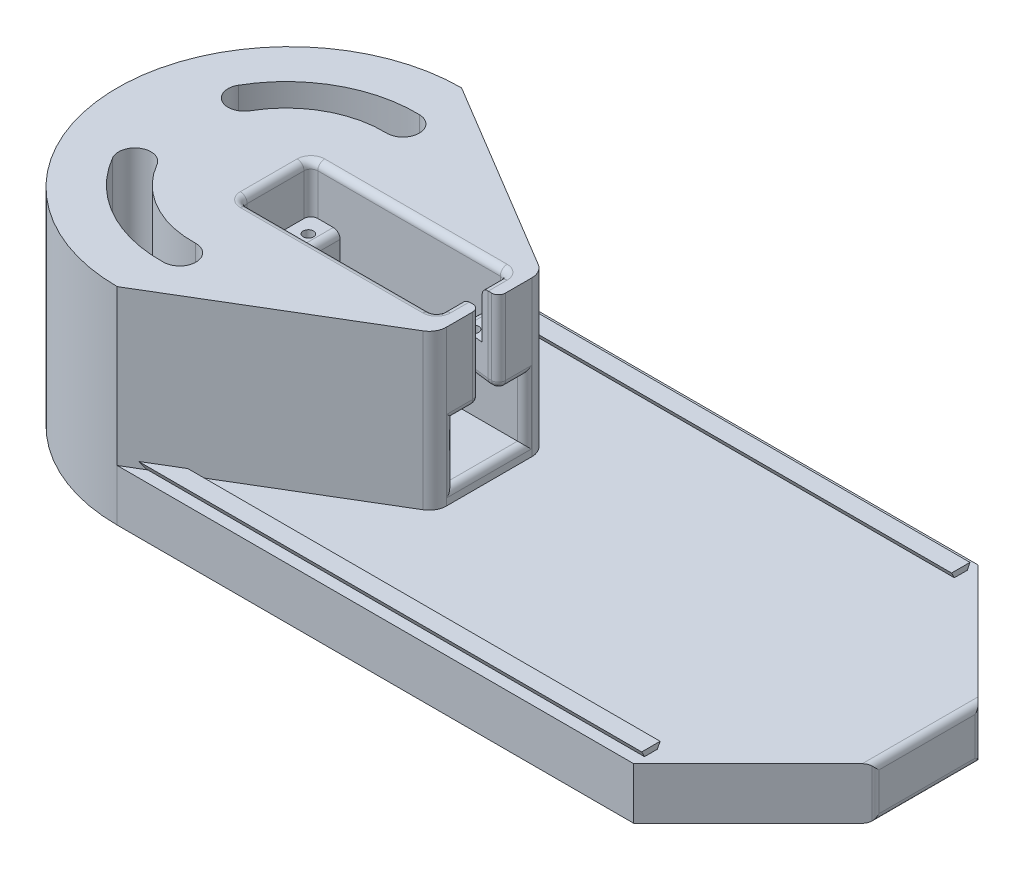
SolidWorks part; units mm, degrees
ref_plane "Front Plane" through (0, 0, 0) normal (0, 0, 1) x (1, 0, 0)
ref_plane "Top Plane" through (0, 0, 0) normal (0, 1, 0) x (1, 0, 0)
ref_plane "Right Plane" through (0, 0, 0) normal (1, 0, 0) x (0, 0, -1)
sketch "Sketch1" plane through (0, 0, 0) normal (0, 1, 0) x (1, 0, 0)
  line L0 (0, 50) -> (150, 50)
  line L1 (150, 50) -> (185.1963, 14.8037)
  line L2 (185.1963, 14.8037) -> (185.1963, -14.8037)
  line L3 (185.1963, -14.8037) -> (150, -50)
  line L4 (150, -50) -> (0, -50)
  line L5 (150, 50) -> (150, -50) construction
  line L6 (150, 0) -> (185.1963, 0) construction
  circle A0 centre (0, 0) radius 50
  dimension "D1" = 100
  dimension "D2" = 45
  dimension "D3" = 150
extrude "Boss-Extrude1" add sketch "Sketch1" against normal blind 60 contours A0 | A0 L4 L3 L2 L1 L0 region at (106.0867, 0, 0) region at (0, 0, 0)
sketch "Sketch2" plane through (0, 0, 0) normal (0, 1, 0) x (1, 0, 0)
  line L0 (0, 0) -> (0, 17.9756)
  line L1 (-0.8835, 15.9756) -> (-0.5, 17.9756) construction
  line L2 (-0.5, 17.9756) -> (0.5, 17.9756) construction
  line L3 (0, 16) -> (0, 17.9756)
  line L4 (0.8835, 15.9756) -> (0.5, 17.9756) construction
  line L5 (1.9041, 15.8863) -> (2.629, 17.7893) construction
  line L6 (2.629, 17.7893) -> (3.6138, 17.6157) construction
  line L7 (3.6442, 15.5795) -> (3.6138, 17.6157) construction
  line L8 (4.6338, 15.3143) -> (5.6782, 17.0625) construction
  line L9 (5.6782, 17.0625) -> (6.6179, 16.7205) construction
  line L10 (6.2942, 14.71) -> (6.6179, 16.7205) construction
  line L11 (7.2227, 14.277) -> (8.5548, 15.8173) construction
  line L12 (8.5548, 15.8173) -> (9.4208, 15.3173) construction
  line L13 (8.7529, 13.3935) -> (9.4208, 15.3173) construction
  line L14 (9.5921, 12.8059) -> (11.1715, 14.0915) construction
  line L15 (11.1715, 14.0915) -> (11.9375, 13.4487) construction
  line L16 (10.9457, 11.6701) -> (11.9375, 13.4487) construction
  line L17 (11.6701, 10.9457) -> (13.4487, 11.9375) construction
  line L18 (13.4487, 11.9375) -> (14.0915, 11.1715) construction
  line L19 (12.8059, 9.5921) -> (14.0915, 11.1715) construction
  line L20 (13.3935, 8.7529) -> (15.3173, 9.4208) construction
  line L21 (15.3173, 9.4208) -> (15.8173, 8.5548) construction
  line L22 (14.277, 7.2227) -> (15.8173, 8.5548) construction
  line L23 (14.71, 6.2942) -> (16.7205, 6.6179) construction
  line L24 (16.7205, 6.6179) -> (17.0625, 5.6782) construction
  line L25 (15.3143, 4.6338) -> (17.0625, 5.6782) construction
  line L26 (15.5795, 3.6442) -> (17.6157, 3.6138) construction
  line L27 (17.6157, 3.6138) -> (17.7893, 2.629) construction
  line L28 (15.8863, 1.9041) -> (17.7893, 2.629) construction
  line L29 (15.9756, 0.8835) -> (17.9756, 0.5) construction
  line L30 (17.9756, 0.5) -> (17.9756, -0.5) construction
  line L31 (15.9756, -0.8835) -> (17.9756, -0.5) construction
  line L32 (15.8863, -1.9041) -> (17.7893, -2.629) construction
  line L33 (17.7893, -2.629) -> (17.6157, -3.6138) construction
  line L34 (15.5795, -3.6442) -> (17.6157, -3.6138) construction
  line L35 (15.3143, -4.6338) -> (17.0625, -5.6782) construction
  line L36 (17.0625, -5.6782) -> (16.7205, -6.6179) construction
  line L37 (14.71, -6.2942) -> (16.7205, -6.6179) construction
  line L38 (14.277, -7.2227) -> (15.8173, -8.5548) construction
  line L39 (15.8173, -8.5548) -> (15.3173, -9.4208) construction
  line L40 (13.3935, -8.7529) -> (15.3173, -9.4208) construction
  line L41 (12.8059, -9.5921) -> (14.0915, -11.1715) construction
  line L42 (14.0915, -11.1715) -> (13.4487, -11.9375) construction
  line L43 (11.6701, -10.9457) -> (13.4487, -11.9375) construction
  line L44 (10.9457, -11.6701) -> (11.9375, -13.4487) construction
  line L45 (11.9375, -13.4487) -> (11.1715, -14.0915) construction
  line L46 (9.5921, -12.8059) -> (11.1715, -14.0915) construction
  line L47 (8.7529, -13.3935) -> (9.4208, -15.3173) construction
  line L48 (9.4208, -15.3173) -> (8.5548, -15.8173) construction
  line L49 (7.2227, -14.277) -> (8.5548, -15.8173) construction
  line L50 (6.2942, -14.71) -> (6.6179, -16.7205) construction
  line L51 (6.6179, -16.7205) -> (5.6782, -17.0625) construction
  line L52 (4.6338, -15.3143) -> (5.6782, -17.0625) construction
  line L53 (3.6442, -15.5795) -> (3.6138, -17.6157) construction
  line L54 (3.6138, -17.6157) -> (2.629, -17.7893) construction
  line L55 (1.9041, -15.8863) -> (2.629, -17.7893) construction
  line L56 (0.8835, -15.9756) -> (0.5, -17.9756) construction
  line L57 (0.5, -17.9756) -> (-0.5, -17.9756) construction
  line L58 (-0.8835, -15.9756) -> (-0.5, -17.9756) construction
  line L59 (-1.9041, -15.8863) -> (-2.629, -17.7893) construction
  line L60 (-2.629, -17.7893) -> (-3.6138, -17.6157) construction
  line L61 (-3.6442, -15.5795) -> (-3.6138, -17.6157) construction
  line L62 (-4.6338, -15.3143) -> (-5.6782, -17.0625) construction
  line L63 (-5.6782, -17.0625) -> (-6.6179, -16.7205) construction
  line L64 (-6.2942, -14.71) -> (-6.6179, -16.7205) construction
  line L65 (-7.2227, -14.277) -> (-8.5548, -15.8173) construction
  line L66 (-8.5548, -15.8173) -> (-9.4208, -15.3173) construction
  line L67 (-8.7529, -13.3935) -> (-9.4208, -15.3173) construction
  line L68 (-9.5921, -12.8059) -> (-11.1715, -14.0915) construction
  line L69 (-11.1715, -14.0915) -> (-11.9375, -13.4487) construction
  line L70 (-10.9457, -11.6701) -> (-11.9375, -13.4487) construction
  line L71 (-11.6701, -10.9457) -> (-13.4487, -11.9375) construction
  line L72 (-13.4487, -11.9375) -> (-14.0915, -11.1715) construction
  line L73 (-12.8059, -9.5921) -> (-14.0915, -11.1715) construction
  line L74 (-13.3935, -8.7529) -> (-15.3173, -9.4208) construction
  line L75 (-15.3173, -9.4208) -> (-15.8173, -8.5548) construction
  line L76 (-14.277, -7.2227) -> (-15.8173, -8.5548) construction
  line L77 (-14.71, -6.2942) -> (-16.7205, -6.6179) construction
  line L78 (-16.7205, -6.6179) -> (-17.0625, -5.6782) construction
  line L79 (-15.3143, -4.6338) -> (-17.0625, -5.6782) construction
  line L80 (-15.5795, -3.6442) -> (-17.6157, -3.6138) construction
  line L81 (-17.6157, -3.6138) -> (-17.7893, -2.629) construction
  line L82 (-15.8863, -1.9041) -> (-17.7893, -2.629) construction
  line L83 (-15.9756, -0.8835) -> (-17.9756, -0.5) construction
  line L84 (-17.9756, -0.5) -> (-17.9756, 0.5) construction
  line L85 (-15.9756, 0.8835) -> (-17.9756, 0.5) construction
  line L86 (-15.8863, 1.9041) -> (-17.7893, 2.629) construction
  line L87 (-17.7893, 2.629) -> (-17.6157, 3.6138) construction
  line L88 (-15.5795, 3.6442) -> (-17.6157, 3.6138) construction
  line L89 (-15.3143, 4.6338) -> (-17.0625, 5.6782) construction
  line L90 (-17.0625, 5.6782) -> (-16.7205, 6.6179) construction
  line L91 (-14.71, 6.2942) -> (-16.7205, 6.6179) construction
  line L92 (-14.277, 7.2227) -> (-15.8173, 8.5548) construction
  line L93 (-15.8173, 8.5548) -> (-15.3173, 9.4208) construction
  line L94 (-13.3935, 8.7529) -> (-15.3173, 9.4208) construction
  line L95 (-12.8059, 9.5921) -> (-14.0915, 11.1715) construction
  line L96 (-14.0915, 11.1715) -> (-13.4487, 11.9375) construction
  line L97 (-11.6701, 10.9457) -> (-13.4487, 11.9375) construction
  line L98 (-10.9457, 11.6701) -> (-11.9375, 13.4487) construction
  line L99 (-11.9375, 13.4487) -> (-11.1715, 14.0915) construction
  line L100 (-9.5921, 12.8059) -> (-11.1715, 14.0915) construction
  line L101 (-8.7529, 13.3935) -> (-9.4208, 15.3173) construction
  line L102 (-9.4208, 15.3173) -> (-8.5548, 15.8173) construction
  line L103 (-7.2227, 14.277) -> (-8.5548, 15.8173) construction
  line L104 (-6.2942, 14.71) -> (-6.6179, 16.7205) construction
  line L105 (-6.6179, 16.7205) -> (-5.6782, 17.0625) construction
  line L106 (-4.6338, 15.3143) -> (-5.6782, 17.0625) construction
  line L107 (-3.6442, 15.5795) -> (-3.6138, 17.6157) construction
  line L108 (-3.6138, 17.6157) -> (-2.629, 17.7893) construction
  line L109 (-1.9041, 15.8863) -> (-2.629, 17.7893) construction
  line L110 (0, 0) -> (56.068, 0) construction
  line L111 (34.5, 0) -> (33.3304, 50.2175) construction
  line L112 (34.5, 0) -> (185.1963, 0) construction
  line L114 (44.5, -10.25) -> (4.5, -10.25)
  line L115 (44.5, -10.25) -> (44.5, 10.25)
  line L116 (44.5, 10.25) -> (4.5, 10.25)
  line L117 (4.5, -10.25) -> (4.5, 10.25)
  line L118 (44.5, -10.25) -> (4.5, 10.25) construction
  line L119 (44.5, 10.25) -> (4.5, -10.25) construction
  circle A0 centre (0, 0) radius 11 construction
  circle A1 centre (0, 0) radius 16 construction
  circle A2 centre (34.5, 0) radius 16
  circle A3 centre (34.5, 0) radius 2.5
  point P10 (24.5, 0)
  point P153 (0, 0)
  dimension "D1" = 22
  dimension "D2" = 32
  dimension "D8" = 32
  dimension "D10" = 5
  dimension "D3" = 2
  dimension "D4" = 0.5
  dimension "D5" = 0.8835
  dimension "D7" = 1.0245
  dimension "D9" = 34.5
  dimension "D11" = 50.2175
  dimension "D12" = 150.6963
  dimension "D13" = 40
  dimension "D14" = 10
  dimension "D15" = 20.5
  dimension "D6" = 36
extrude "Cut-Extrude1" cut sketch "Sketch2" against normal blind 41 contours A2 L116 L117 L114 | A3 | L116 A2 L114 L115 A3 region at (31.9657, 0, 0) region at (12.1259, 0, 0) region at (34.5, 0, 0)
sketch "Sketch3" plane through (0, 0, 0) normal (0, 1, 0) x (1, 0, 0)
  line L0 (0.5, 5) -> (0.5, -5) construction
  line L1 (44.5, -10.25) -> (4.5, -10.25)
  line L2 (44.5, -10.25) -> (44.5, 10.25)
  line L3 (44.5, 10.25) -> (4.5, 10.25)
  line L4 (4.5, -10.25) -> (4.5, 10.25)
  line L5 (44.5, -10.25) -> (4.5, 10.25) construction
  line L6 (44.5, 10.25) -> (4.5, -10.25) construction
  line L7 (53, -10.25) -> (-4, -10.25)
  line L8 (53, -10.25) -> (53, 10.25)
  line L9 (53, 10.25) -> (-4, 10.25)
  line L10 (-4, -10.25) -> (-4, 10.25)
  line L11 (53, -10.25) -> (-4, 10.25) construction
  line L12 (53, 10.25) -> (-4, -10.25) construction
  line L13 (24.5, 6.4341) -> (24.5, -6.9886) construction
  line L14 (48.5, 5) -> (48.5, -5) construction
  line L15 (58, 15.25) -> (-9, 15.25)
  line L16 (-9, -15.25) -> (-9, 15.25)
  line L17 (58, -15.25) -> (-9, -15.25)
  line L18 (58, -15.25) -> (58, 15.25)
  line L19 (0, 50) -> (150, 50)
  line L20 (150, 50) -> (185.1963, 14.8037)
  line L21 (185.1963, 14.8037) -> (185.1963, -14.8037)
  line L22 (185.1963, -14.8037) -> (150, -50)
  line L23 (150, -50) -> (0, -50)
  line L24 (0, -50) -> (58, -15.25)
  line L25 (0, 50) -> (58, 15.25)
  line L26 (-9, 15.25) -> (-16.5, 28.2404) construction
  line L27 (24.5, 0) -> (-33.0818, 0) construction
  line L28 (-33, 0) -> (33, 0) construction
  circle A0 centre (0.5, 5) radius 1.5
  circle A1 centre (0.5, -5) radius 1.5
  circle A2 centre (48.5, -5) radius 1.5
  circle A3 centre (48.5, 5) radius 1.5
  arc A4 (-29, 15.8925) -> (0.5654, 32.4227) centre (-0.3957, -0.5633) cw construction
  arc A5 (0.7026, 37.1297) -> (-33.0818, 18.2407) centre (-0.3957, -0.5633) ccw
  arc A6 (0.4283, 27.7157) -> (-24.9182, 13.5443) centre (-0.3957, -0.5633) ccw
  arc A7 (0.4283, 27.7157) -> (0.7026, 37.1297) centre (0.5654, 32.4227) ccw
  arc A8 (-33.0818, 18.2407) -> (-24.9182, 13.5443) centre (-29, 15.8925) ccw
  point P0 (24.5, 0)
  point P8 (24.5, 0)
  point P42 (-16.5, 28.2404)
  point P47 (48.5, 0)
  line M15 (0, -50) -> (150, -50)
  line M16 (150, -50) -> (185.1963, -14.8037)
  line M17 (185.1963, -14.8037) -> (185.1963, 14.8037)
  line M18 (185.1963, 14.8037) -> (150, 50)
  line M19 (150, 50) -> (0, 50)
  line M20 (44.5, 10.25) -> (44.5, -10.25)
  line M22 (4.5, -10.25) -> (4.5, 10.25)
  dimension "D4" = 3
  dimension "D5" = 48
  dimension "D9" = 33
  dimension "D1" = 10
  dimension "D2" = 20.5
  dimension "D3" = 57
  dimension "D7" = 120
  dimension "D8" = 15
  dimension "D10" = 20
  dimension "D6" = 5
extrude "Cut-Extrude2" cut sketch "Sketch3" against normal blind 14 contours L10 L7 L9 A1 A0 M22 | L8 L9 L7 A2 A3 M20 region at (48.7721, 0, 0) region at (0.2279, 0, 0)
extrude "Cut-Extrude3" cut sketch "Sketch3<3>" against normal blind 19 contours A0 | A1 | A3 | A2 region at (0.5, 0, -5) region at (0.5, 0, 5) region at (48.5, 0, 5) region at (48.5, 0, -5)
sketch "Sketch3<3>" plane through (0, 0, 0) normal (0, 1, 0) x (1, 0, 0) same geometry as "Sketch3"
extrude "Cut-Extrude4" cut sketch "Sketch3<4>" against normal blind 45 contours L25 L18 L24 M19 M15 M16 M17 M18 region at (104.4529, 0, 0)
sketch "Sketch3<4>" plane through (0, 0, 0) normal (0, 1, 0) x (1, 0, 0) same geometry as "Sketch3"
extrude "Cut-Extrude5" cut sketch "Sketch3<5>" against normal blind 45 contours A5 A8 A6 A7 region at (-15.471, 0, -26.3999)
sketch "Sketch3<5>" plane through (0, 0, 0) normal (0, 1, 0) x (1, 0, 0) same geometry as "Sketch3"
mirror "Mirror1" about plane through (0, 0, 0) normal (0, 0, 1) of "Cut-Extrude5"
sketch "Sketch6" plane through (44.5, 0, 0) normal (-1, 0, 0) x (0, 0, 1)
  line L0 (10.25, -24) -> (-10.25, -24)
  line L1 (-10.25, -41.1911) -> (10.25, -41.1911)
  line L2 (-10.25, -41.1911) -> (-10.25, -14)
  line L3 (-10.25, -14) -> (10.25, -14)
  line L4 (10.25, -41.1911) -> (10.25, -14)
  line L5 (-10.25, -41.1911) -> (10.25, -14) construction
  line L6 (-10.25, -14) -> (10.25, -41.1911) construction
  point P0 (0, -27.5955)
  line M7 (-10.25, -14) -> (-10.25, -41)
  line M8 (-10.25, -41) -> (10.25, -41)
  line M9 (10.25, -41) -> (10.25, -14)
  dimension "D1" = 10
extrude "Cut-Extrude6" cut sketch "Sketch6" against normal blind 45 contours L0 M9 M7 M8 region at (44.5, -32.5, 0)
fillet "Fillet1" radius 2 1 edges at (44.5, -24, 0)
fillet "Fillet2" radius 2 2 edges at (44.5, -14, 0) (4.5, -14, 0)
fillet "Fillet3" radius 5 2 edges at (58, -22.5, 15.25) (58, -22.5, -15.25)
fillet "Fillet4" radius 2 8 edges at (53, 0, 0) (24.5, 0, 10.25) (24.5, 0, -10.25) (-4, 0, 0) (-4, -7, -10.25) (-4, -7, 10.25) (53, -7, 10.25) (53, -7, -10.25)
fillet "Fillet5" radius 2 4 edges at (58, -32.5, 10.25) (58, -32.5, -10.25) (58, -41, 0) (58, -24, 0)
ref_plane "Plane1" through (150, 0, 0) normal (-1, 0, 0) x (0, 0, 1)
sketch "Sketch8" plane through (150, 0, 0) normal (-1, 0, 0) x (0, 0, 1)
  line L0 (50, -45) -> (40, -45)
  line L1 (50, -45) -> (14.8037, -45) construction
  line L2 (45, -43) -> (45, -39.3584) construction
  line L3 (47, -45) -> (48, -43)
  line L4 (48, -43) -> (42, -43)
  line L5 (43, -45) -> (42, -43)
  line L6 (47, -45) -> (43, -45)
  line L7 (47.6764, -43.2) -> (42.3236, -43.2)
  line L8 (43.1236, -44.8) -> (42.3236, -43.2)
  line L9 (46.8764, -44.8) -> (43.1236, -44.8)
  line L10 (46.8764, -44.8) -> (47.6764, -43.2)
  line L11 (47.6764, -43.2) -> (46.7102, -45.1325)
  line L12 (46.7102, -45.1325) -> (43.2898, -45.1325)
  line L13 (43.2898, -45.1325) -> (42.3236, -43.2)
  point P12 (45, -43)
  dimension "D1" = 10
  dimension "D2" = 3
  dimension "D3" = 4
  dimension "D4" = 2
  dimension "D5" = 63.435
  dimension "D6" = 0.2
extrude "Boss-Extrude2" add sketch "Sketch8" along normal blind 146 contours L9 L10 L7 L8 region at (150, -43.9531, 45)
mirror "Mirror2" about plane through (0, 0, 0) normal (0, 0, 1) of "Boss-Extrude2"
sketch "Sketch9" plane through (0, 0, 0) normal (0, 1, 0) x (1, 0, 0)
  line L0 (42.3935, 0) -> (56.9578, 0) construction
  line L1 (44.5, 4) -> (44.5, -4)
  line L2 (44.5, -4) -> (55, -2.75)
  line L3 (55, 8.25) -> (55, -8.25) construction
  line L4 (55, -2.75) -> (55, 2.75)
  line L5 (55, 2.75) -> (44.5, 4)
  line L6 (44.5, -10.25) -> (44.5, 10.25) construction
  line L7 (55, 2.75) -> (58, 2.75)
  line L8 (58, -12.417) -> (58, 12.417) construction
  line L9 (58, 2.75) -> (58, -2.75)
  line L10 (58, -2.75) -> (55, -2.75)
  point P5 (44.5, 0)
  point P10 (55, 0)
  line M8 (58, -12.417) -> (58, 12.417)
  line M21 (55, 8.25) -> (55, -8.25)
  dimension "D1" = 8
  dimension "D2" = 5.5
extrude "Cut-Extrude7" cut sketch "Sketch9" against normal blind 29 contours L1 L0 L5 M21 | L0 L1 L2 L4 | L10 L7 L4 M8 M21 region at (49.4259, 0, -1.7068) region at (49.4259, 0, 1.7068) region at (55.0626, 0, -1.375)
fillet "Fillet7" radius 2 20 edges at (47.2553, -14, -3.672) (45.0858, -14.5858, -3.9303) (44.5, -19, -4) (45.0858, -23.4142, -3.9303) (47.2553, -14, 3.672) (45.0858, -14.5858, 3.9303) (44.5, -19, 4) (45.0858, -23.4142, 3.9303) (55.5, -24, -2.75) (57.4142, -23.4142, -2.75) (55.5, -24, 2.75) (57.4142, -23.4142, 2.75) (185.1963, -52.5, -14.8037) (185.1963, -60, 0) (185.1963, -52.5, 14.8037) (185.1963, -45, 0) (50.75, -24, -3.256) (50.75, -24, 3.256) (58, -11, -2.75) (58, -11, 2.75)
